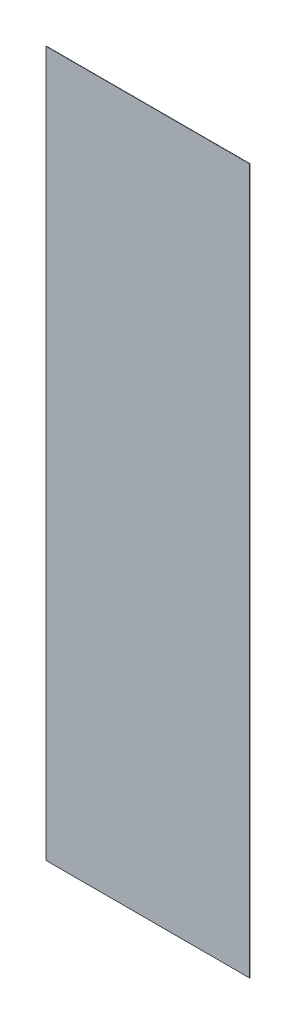
SolidWorks part; units mm, degrees
material "Ti-6Al-4VSolution treated and aged (SS)"
ref_plane "Front Plane" through (0, 0, 0) normal (0, 0, 1) x (1, 0, 0)
ref_plane "Top Plane" through (0, 0, 0) normal (0, 1, 0) x (1, 0, 0)
ref_plane "Right Plane" through (0, 0, 0) normal (1, 0, 0) x (0, 0, -1)
sketch "Sketch3" plane through (0, 0, 0) normal (0, 1, 0) x (1, 0, 0)
  line L0 (-693.76, 0) -> (693.76, 0)
  line L1 (693.76, 0) -> (694.3374, 1)
  line L2 (694.3374, 1) -> (-694.3374, 1)
  line L3 (0, 0) -> (0, 738.7484) construction
  line L5 (0, 1) -> (0, 0) construction
  line L6 (-693.76, 0) -> (-694.3374, 1)
  dimension "D1" = 693.76
  dimension "D2" = 120
  dimension "D3" = 1
extrude "Boss-Extrude1" add sketch "Sketch3" against normal blind 4810
chamfer "Chamfer1" distance 1 angle 45 1 edges at (0, 0, 0)
sketch "Sketch5" plane through (-521.1854, 0, -300.9065) normal (-0.866, 0, -0.5) x (-0.5, 0, 0.866)
  circle A0 centre (485.0344, -4772) radius 4.7625
  circle A1 centre (535.0344, -4772) radius 4.7625
  circle A2 centre (585.0344, -4772) radius 4.7625
  circle A3 centre (635.0344, -4772) radius 4.7625
  circle A4 centre (685.0344, -4772) radius 4.7625
  circle A5 centre (735.0344, -4772) radius 4.7625
  circle A6 centre (785.0344, -4772) radius 4.7625
  circle A7 centre (835.0344, -4772) radius 4.7625
  circle A8 centre (885.0344, -4772) radius 4.7625
  circle A9 centre (935.0344, -4772) radius 4.7625
  circle A10 centre (985.0344, -4772) radius 4.7625
  circle A11 centre (1035.0344, -4772) radius 4.7625
  circle A12 centre (1085.0344, -4772) radius 4.7625
  circle A13 centre (1135.0344, -4772) radius 4.7625
  circle A14 centre (1185.0344, -4772) radius 4.7625
  circle A15 centre (1235.0344, -4772) radius 4.7625
  circle A16 centre (1285.0344, -4772) radius 4.7625
  circle A17 centre (1335.0344, -4772) radius 4.7625
  circle A18 centre (1385.0344, -4772) radius 4.7625
  circle A19 centre (1435.0344, -4772) radius 4.7625
  circle A20 centre (1485.0344, -4772) radius 4.7625
  circle A21 centre (1535.0344, -4772) radius 4.7625
  circle A22 centre (1585.0344, -4772) radius 4.7625
  circle A23 centre (535.0344, -222) radius 4.7625
  circle A24 centre (585.0344, -222) radius 4.7625
  circle A25 centre (635.0344, -222) radius 4.7625
  circle A26 centre (685.0344, -222) radius 4.7625
  circle A27 centre (735.0344, -222) radius 4.7625
  circle A28 centre (785.0344, -222) radius 4.7625
  circle A29 centre (835.0344, -222) radius 4.7625
  circle A30 centre (885.0344, -222) radius 4.7625
  circle A31 centre (935.0344, -222) radius 4.7625
  circle A32 centre (985.0344, -222) radius 4.7625
  circle A33 centre (1035.0344, -222) radius 4.7625
  circle A34 centre (1085.0344, -222) radius 4.7625
  circle A35 centre (1135.0344, -222) radius 4.7625
  circle A36 centre (1185.0344, -222) radius 4.7625
  circle A37 centre (1235.0344, -222) radius 4.7625
  circle A38 centre (1285.0344, -222) radius 4.7625
  circle A39 centre (1335.0344, -222) radius 4.7625
  circle A40 centre (1385.0344, -222) radius 4.7625
  circle A41 centre (1435.0344, -222) radius 4.7625
  circle A42 centre (1485.0344, -222) radius 4.7625
  circle A43 centre (1535.0344, -222) radius 4.7625
  circle A44 centre (1585.0344, -222) radius 4.7625
  circle A45 centre (485.0344, -222) radius 4.7625
  circle A46 centre (1035.0344, -222) radius 4.7625
  circle A47 centre (1035.0344, -272) radius 4.7625
  circle A48 centre (1035.0344, -322) radius 4.7625
  circle A49 centre (1035.0344, -372) radius 4.7625
  circle A50 centre (1035.0344, -422) radius 4.7625
  circle A51 centre (1035.0344, -472) radius 4.7625
  circle A52 centre (1035.0344, -522) radius 4.7625
  circle A53 centre (1035.0344, -572) radius 4.7625
  circle A54 centre (1035.0344, -622) radius 4.7625
  circle A55 centre (1035.0344, -672) radius 4.7625
  circle A56 centre (1035.0344, -722) radius 4.7625
  circle A57 centre (1035.0344, -772) radius 4.7625
  circle A58 centre (1035.0344, -822) radius 4.7625
  circle A59 centre (1035.0344, -872) radius 4.7625
  circle A60 centre (1035.0344, -922) radius 4.7625
  circle A61 centre (1035.0344, -972) radius 4.7625
  circle A62 centre (1035.0344, -1022) radius 4.7625
  circle A63 centre (1035.0344, -1072) radius 4.7625
  circle A64 centre (1035.0344, -1122) radius 4.7625
  circle A65 centre (1035.0344, -1172) radius 4.7625
  circle A66 centre (1035.0344, -1222) radius 4.7625
  circle A67 centre (1035.0344, -1272) radius 4.7625
  circle A68 centre (1035.0344, -1322) radius 4.7625
  circle A69 centre (1035.0344, -1372) radius 4.7625
  circle A70 centre (1035.0344, -1422) radius 4.7625
  circle A71 centre (1035.0344, -1472) radius 4.7625
  circle A72 centre (1035.0344, -1522) radius 4.7625
  circle A73 centre (1035.0344, -1572) radius 4.7625
  circle A74 centre (1035.0344, -1622) radius 4.7625
  circle A75 centre (1035.0344, -1672) radius 4.7625
  circle A76 centre (1035.0344, -1722) radius 4.7625
  circle A77 centre (1035.0344, -1772) radius 4.7625
  circle A78 centre (1035.0344, -1822) radius 4.7625
  circle A79 centre (1035.0344, -1872) radius 4.7625
  circle A80 centre (1035.0344, -1922) radius 4.7625
  circle A81 centre (1035.0344, -1972) radius 4.7625
  circle A82 centre (1035.0344, -2022) radius 4.7625
  circle A83 centre (1035.0344, -2072) radius 4.7625
  circle A84 centre (1035.0344, -2122) radius 4.7625
  circle A85 centre (1035.0344, -2172) radius 4.7625
  circle A86 centre (1035.0344, -2222) radius 4.7625
  circle A87 centre (1035.0344, -2272) radius 4.7625
  circle A88 centre (1035.0344, -2322) radius 4.7625
  circle A89 centre (1035.0344, -2372) radius 4.7625
  circle A90 centre (1035.0344, -2422) radius 4.7625
  circle A91 centre (1035.0344, -2472) radius 4.7625
  circle A92 centre (1035.0344, -2522) radius 4.7625
  circle A93 centre (1035.0344, -2572) radius 4.7625
  circle A94 centre (1035.0344, -2622) radius 4.7625
  circle A95 centre (1035.0344, -2672) radius 4.7625
  circle A96 centre (1035.0344, -2722) radius 4.7625
  circle A97 centre (1035.0344, -2772) radius 4.7625
  circle A98 centre (1035.0344, -2822) radius 4.7625
  circle A99 centre (1035.0344, -2872) radius 4.7625
  circle A100 centre (1035.0344, -2922) radius 4.7625
  circle A101 centre (1035.0344, -2972) radius 4.7625
  circle A102 centre (1035.0344, -3022) radius 4.7625
  circle A103 centre (1035.0344, -3072) radius 4.7625
  circle A104 centre (1035.0344, -3122) radius 4.7625
  circle A105 centre (1035.0344, -3172) radius 4.7625
  circle A106 centre (1035.0344, -3222) radius 4.7625
  circle A107 centre (1035.0344, -3272) radius 4.7625
  circle A108 centre (1035.0344, -3322) radius 4.7625
  circle A109 centre (1035.0344, -3372) radius 4.7625
  circle A110 centre (1035.0344, -3422) radius 4.7625
  circle A111 centre (1035.0344, -3472) radius 4.7625
  circle A112 centre (1035.0344, -3522) radius 4.7625
  circle A113 centre (1035.0344, -3572) radius 4.7625
  circle A114 centre (1035.0344, -3622) radius 4.7625
  circle A115 centre (1035.0344, -3672) radius 4.7625
  circle A116 centre (1035.0344, -3722) radius 4.7625
  circle A117 centre (1035.0344, -3772) radius 4.7625
  circle A118 centre (1035.0344, -3822) radius 4.7625
  circle A119 centre (1035.0344, -3872) radius 4.7625
  circle A120 centre (1035.0344, -3922) radius 4.7625
  circle A121 centre (1035.0344, -3972) radius 4.7625
  circle A122 centre (1035.0344, -4022) radius 4.7625
  circle A123 centre (1035.0344, -4072) radius 4.7625
  circle A124 centre (1035.0344, -4122) radius 4.7625
  circle A125 centre (1035.0344, -4172) radius 4.7625
  circle A126 centre (1035.0344, -4222) radius 4.7625
  circle A127 centre (1035.0344, -4272) radius 4.7625
  circle A128 centre (1035.0344, -4322) radius 4.7625
  circle A129 centre (1035.0344, -4372) radius 4.7625
  circle A130 centre (1035.0344, -4422) radius 4.7625
  circle A131 centre (1035.0344, -4472) radius 4.7625
  circle A132 centre (1035.0344, -4522) radius 4.7625
  circle A133 centre (1035.0344, -4572) radius 4.7625
  circle A134 centre (1035.0344, -4622) radius 4.7625
  circle A135 centre (1035.0344, -4672) radius 4.7625
  circle A136 centre (1035.0344, -4722) radius 4.7625
  circle A137 centre (1035.0344, -4772) radius 4.7625
  circle A138 centre (485.0344, -272) radius 4.7625
  circle A139 centre (485.0344, -322) radius 4.7625
  circle A140 centre (485.0344, -372) radius 4.7625
  circle A141 centre (485.0344, -422) radius 4.7625
  circle A142 centre (485.0344, -472) radius 4.7625
  circle A143 centre (485.0344, -522) radius 4.7625
  circle A144 centre (485.0344, -572) radius 4.7625
  circle A145 centre (485.0344, -622) radius 4.7625
  circle A146 centre (485.0344, -672) radius 4.7625
  circle A147 centre (485.0344, -722) radius 4.7625
  circle A148 centre (485.0344, -772) radius 4.7625
  circle A149 centre (485.0344, -822) radius 4.7625
  circle A150 centre (485.0344, -872) radius 4.7625
  circle A151 centre (485.0344, -922) radius 4.7625
  circle A152 centre (485.0344, -972) radius 4.7625
  circle A153 centre (485.0344, -1022) radius 4.7625
  circle A154 centre (485.0344, -1072) radius 4.7625
  circle A155 centre (485.0344, -1122) radius 4.7625
  circle A156 centre (485.0344, -1172) radius 4.7625
  circle A157 centre (485.0344, -1222) radius 4.7625
  circle A158 centre (485.0344, -1272) radius 4.7625
  circle A159 centre (485.0344, -1322) radius 4.7625
  circle A160 centre (485.0344, -1372) radius 4.7625
  circle A161 centre (485.0344, -1422) radius 4.7625
  circle A162 centre (485.0344, -1472) radius 4.7625
  circle A163 centre (485.0344, -1522) radius 4.7625
  circle A164 centre (485.0344, -1572) radius 4.7625
  circle A165 centre (485.0344, -1622) radius 4.7625
  circle A166 centre (485.0344, -1672) radius 4.7625
  circle A167 centre (485.0344, -1722) radius 4.7625
  circle A168 centre (485.0344, -1772) radius 4.7625
  circle A169 centre (485.0344, -1822) radius 4.7625
  circle A170 centre (485.0344, -1872) radius 4.7625
  circle A171 centre (485.0344, -1922) radius 4.7625
  circle A172 centre (485.0344, -1972) radius 4.7625
  circle A173 centre (485.0344, -2022) radius 4.7625
  circle A174 centre (485.0344, -2072) radius 4.7625
  circle A175 centre (485.0344, -2122) radius 4.7625
  circle A176 centre (485.0344, -2172) radius 4.7625
  circle A177 centre (485.0344, -2222) radius 4.7625
  circle A178 centre (485.0344, -2272) radius 4.7625
  circle A179 centre (485.0344, -2322) radius 4.7625
  circle A180 centre (485.0344, -2372) radius 4.7625
  circle A181 centre (485.0344, -2422) radius 4.7625
  circle A182 centre (485.0344, -2472) radius 4.7625
  circle A183 centre (485.0344, -2522) radius 4.7625
  circle A184 centre (485.0344, -2572) radius 4.7625
  circle A185 centre (485.0344, -2622) radius 4.7625
  circle A186 centre (485.0344, -2672) radius 4.7625
  circle A187 centre (485.0344, -2722) radius 4.7625
  circle A188 centre (485.0344, -2772) radius 4.7625
  circle A189 centre (485.0344, -2822) radius 4.7625
  circle A190 centre (485.0344, -2872) radius 4.7625
  circle A191 centre (485.0344, -2922) radius 4.7625
  circle A192 centre (485.0344, -2972) radius 4.7625
  circle A193 centre (485.0344, -3022) radius 4.7625
  circle A194 centre (485.0344, -3072) radius 4.7625
  circle A195 centre (485.0344, -3122) radius 4.7625
  circle A196 centre (485.0344, -3172) radius 4.7625
  circle A197 centre (485.0344, -3222) radius 4.7625
  circle A198 centre (485.0344, -3272) radius 4.7625
  circle A199 centre (485.0344, -3322) radius 4.7625
  circle A200 centre (485.0344, -3372) radius 4.7625
  circle A201 centre (485.0344, -3422) radius 4.7625
  circle A202 centre (485.0344, -3472) radius 4.7625
  circle A203 centre (485.0344, -3522) radius 4.7625
  circle A204 centre (485.0344, -3572) radius 4.7625
  circle A205 centre (485.0344, -3622) radius 4.7625
  circle A206 centre (485.0344, -3672) radius 4.7625
  circle A207 centre (485.0344, -3722) radius 4.7625
  circle A208 centre (485.0344, -3772) radius 4.7625
  circle A209 centre (485.0344, -3822) radius 4.7625
  circle A210 centre (485.0344, -3872) radius 4.7625
  circle A211 centre (485.0344, -3922) radius 4.7625
  circle A212 centre (485.0344, -3972) radius 4.7625
  circle A213 centre (485.0344, -4022) radius 4.7625
  circle A214 centre (485.0344, -4072) radius 4.7625
  circle A215 centre (485.0344, -4122) radius 4.7625
  circle A216 centre (485.0344, -4172) radius 4.7625
  circle A217 centre (485.0344, -4222) radius 4.7625
  circle A218 centre (485.0344, -4272) radius 4.7625
  circle A219 centre (485.0344, -4322) radius 4.7625
  circle A220 centre (485.0344, -4372) radius 4.7625
  circle A221 centre (485.0344, -4422) radius 4.7625
  circle A222 centre (485.0344, -4472) radius 4.7625
  circle A223 centre (485.0344, -4522) radius 4.7625
  circle A224 centre (485.0344, -4572) radius 4.7625
  circle A225 centre (485.0344, -4622) radius 4.7625
  circle A226 centre (485.0344, -4672) radius 4.7625
  circle A227 centre (485.0344, -4722) radius 4.7625
  circle A228 centre (485.0344, -4772) radius 4.7625
  circle A229 centre (1035.0344, -4772) radius 4.7625
  circle A230 centre (1585.0344, -4772) radius 4.7625
  circle A231 centre (1035.0344, -4722) radius 4.7625
  circle A232 centre (1585.0344, -4722) radius 4.7625
  circle A233 centre (1035.0344, -4672) radius 4.7625
  circle A234 centre (1585.0344, -4672) radius 4.7625
  circle A235 centre (1035.0344, -4622) radius 4.7625
  circle A236 centre (1585.0344, -4622) radius 4.7625
  circle A237 centre (1035.0344, -4572) radius 4.7625
  circle A238 centre (1585.0344, -4572) radius 4.7625
  circle A239 centre (1035.0344, -4522) radius 4.7625
  circle A240 centre (1585.0344, -4522) radius 4.7625
  circle A241 centre (1035.0344, -4472) radius 4.7625
  circle A242 centre (1585.0344, -4472) radius 4.7625
  circle A243 centre (1035.0344, -4422) radius 4.7625
  circle A244 centre (1585.0344, -4422) radius 4.7625
  circle A245 centre (1035.0344, -4372) radius 4.7625
  circle A246 centre (1585.0344, -4372) radius 4.7625
  circle A247 centre (1035.0344, -4322) radius 4.7625
  circle A248 centre (1585.0344, -4322) radius 4.7625
  circle A249 centre (1035.0344, -4272) radius 4.7625
  circle A250 centre (1585.0344, -4272) radius 4.7625
  circle A251 centre (1035.0344, -4222) radius 4.7625
  circle A252 centre (1585.0344, -4222) radius 4.7625
  circle A253 centre (1035.0344, -4172) radius 4.7625
  circle A254 centre (1585.0344, -4172) radius 4.7625
  circle A255 centre (1035.0344, -4122) radius 4.7625
  circle A256 centre (1585.0344, -4122) radius 4.7625
  circle A257 centre (1035.0344, -4072) radius 4.7625
  circle A258 centre (1585.0344, -4072) radius 4.7625
  circle A259 centre (1035.0344, -4022) radius 4.7625
  circle A260 centre (1585.0344, -4022) radius 4.7625
  circle A261 centre (1035.0344, -3972) radius 4.7625
  circle A262 centre (1585.0344, -3972) radius 4.7625
  circle A263 centre (1035.0344, -3922) radius 4.7625
  circle A264 centre (1585.0344, -3922) radius 4.7625
  circle A265 centre (1035.0344, -3872) radius 4.7625
  circle A266 centre (1585.0344, -3872) radius 4.7625
  circle A267 centre (1035.0344, -3822) radius 4.7625
  circle A268 centre (1585.0344, -3822) radius 4.7625
  circle A269 centre (1035.0344, -3772) radius 4.7625
  circle A270 centre (1585.0344, -3772) radius 4.7625
  circle A271 centre (1035.0344, -3722) radius 4.7625
  circle A272 centre (1585.0344, -3722) radius 4.7625
  circle A273 centre (1035.0344, -3672) radius 4.7625
  circle A274 centre (1585.0344, -3672) radius 4.7625
  circle A275 centre (1035.0344, -3622) radius 4.7625
  circle A276 centre (1585.0344, -3622) radius 4.7625
  circle A277 centre (1035.0344, -3572) radius 4.7625
  circle A278 centre (1585.0344, -3572) radius 4.7625
  circle A279 centre (1035.0344, -3522) radius 4.7625
  circle A280 centre (1585.0344, -3522) radius 4.7625
  circle A281 centre (1035.0344, -3472) radius 4.7625
  circle A282 centre (1585.0344, -3472) radius 4.7625
  circle A283 centre (1035.0344, -3422) radius 4.7625
  circle A284 centre (1585.0344, -3422) radius 4.7625
  circle A285 centre (1035.0344, -3372) radius 4.7625
  circle A286 centre (1585.0344, -3372) radius 4.7625
  circle A287 centre (1035.0344, -3322) radius 4.7625
  circle A288 centre (1585.0344, -3322) radius 4.7625
  circle A289 centre (1035.0344, -3272) radius 4.7625
  circle A290 centre (1585.0344, -3272) radius 4.7625
  circle A291 centre (1035.0344, -3222) radius 4.7625
  circle A292 centre (1585.0344, -3222) radius 4.7625
  circle A293 centre (1035.0344, -3172) radius 4.7625
  circle A294 centre (1585.0344, -3172) radius 4.7625
  circle A295 centre (1035.0344, -3122) radius 4.7625
  circle A296 centre (1585.0344, -3122) radius 4.7625
  circle A297 centre (1035.0344, -3072) radius 4.7625
  circle A298 centre (1585.0344, -3072) radius 4.7625
  circle A299 centre (1035.0344, -3022) radius 4.7625
  circle A300 centre (1585.0344, -3022) radius 4.7625
  circle A301 centre (1035.0344, -2972) radius 4.7625
  circle A302 centre (1585.0344, -2972) radius 4.7625
  circle A303 centre (1035.0344, -2922) radius 4.7625
  circle A304 centre (1585.0344, -2922) radius 4.7625
  circle A305 centre (1035.0344, -2872) radius 4.7625
  circle A306 centre (1585.0344, -2872) radius 4.7625
  circle A307 centre (1035.0344, -2822) radius 4.7625
  circle A308 centre (1585.0344, -2822) radius 4.7625
  circle A309 centre (1035.0344, -2772) radius 4.7625
  circle A310 centre (1585.0344, -2772) radius 4.7625
  circle A311 centre (1035.0344, -2722) radius 4.7625
  circle A312 centre (1585.0344, -2722) radius 4.7625
  circle A313 centre (1035.0344, -2672) radius 4.7625
  circle A314 centre (1585.0344, -2672) radius 4.7625
  circle A315 centre (1035.0344, -2622) radius 4.7625
  circle A316 centre (1585.0344, -2622) radius 4.7625
  circle A317 centre (1035.0344, -2572) radius 4.7625
  circle A318 centre (1585.0344, -2572) radius 4.7625
  circle A319 centre (1035.0344, -2522) radius 4.7625
  circle A320 centre (1585.0344, -2522) radius 4.7625
  circle A321 centre (1035.0344, -2472) radius 4.7625
  circle A322 centre (1585.0344, -2472) radius 4.7625
  circle A323 centre (1035.0344, -2422) radius 4.7625
  circle A324 centre (1585.0344, -2422) radius 4.7625
  circle A325 centre (1035.0344, -2372) radius 4.7625
  circle A326 centre (1585.0344, -2372) radius 4.7625
  circle A327 centre (1035.0344, -2322) radius 4.7625
  circle A328 centre (1585.0344, -2322) radius 4.7625
  circle A329 centre (1035.0344, -2272) radius 4.7625
  circle A330 centre (1585.0344, -2272) radius 4.7625
  circle A331 centre (1035.0344, -2222) radius 4.7625
  circle A332 centre (1585.0344, -2222) radius 4.7625
  circle A333 centre (1035.0344, -2172) radius 4.7625
  circle A334 centre (1585.0344, -2172) radius 4.7625
  circle A335 centre (1035.0344, -2122) radius 4.7625
  circle A336 centre (1585.0344, -2122) radius 4.7625
  circle A337 centre (1035.0344, -2072) radius 4.7625
  circle A338 centre (1585.0344, -2072) radius 4.7625
  circle A339 centre (1035.0344, -2022) radius 4.7625
  circle A340 centre (1585.0344, -2022) radius 4.7625
  circle A341 centre (1035.0344, -1972) radius 4.7625
  circle A342 centre (1585.0344, -1972) radius 4.7625
  circle A343 centre (1035.0344, -1922) radius 4.7625
  circle A344 centre (1585.0344, -1922) radius 4.7625
  circle A345 centre (1035.0344, -1872) radius 4.7625
  circle A346 centre (1585.0344, -1872) radius 4.7625
  circle A347 centre (1035.0344, -1822) radius 4.7625
  circle A348 centre (1585.0344, -1822) radius 4.7625
  circle A349 centre (1035.0344, -1772) radius 4.7625
  circle A350 centre (1585.0344, -1772) radius 4.7625
  circle A351 centre (1035.0344, -1722) radius 4.7625
  circle A352 centre (1585.0344, -1722) radius 4.7625
  circle A353 centre (1035.0344, -1672) radius 4.7625
  circle A354 centre (1585.0344, -1672) radius 4.7625
  circle A355 centre (1035.0344, -1622) radius 4.7625
  circle A356 centre (1585.0344, -1622) radius 4.7625
  circle A357 centre (1035.0344, -1572) radius 4.7625
  circle A358 centre (1585.0344, -1572) radius 4.7625
  circle A359 centre (1035.0344, -1522) radius 4.7625
  circle A360 centre (1585.0344, -1522) radius 4.7625
  circle A361 centre (1035.0344, -1472) radius 4.7625
  circle A362 centre (1585.0344, -1472) radius 4.7625
  circle A363 centre (1035.0344, -1422) radius 4.7625
  circle A364 centre (1585.0344, -1422) radius 4.7625
  circle A365 centre (1035.0344, -1372) radius 4.7625
  circle A366 centre (1585.0344, -1372) radius 4.7625
  circle A367 centre (1035.0344, -1322) radius 4.7625
  circle A368 centre (1585.0344, -1322) radius 4.7625
  circle A369 centre (1035.0344, -1272) radius 4.7625
  circle A370 centre (1585.0344, -1272) radius 4.7625
  circle A371 centre (1035.0344, -1222) radius 4.7625
  circle A372 centre (1585.0344, -1222) radius 4.7625
  circle A373 centre (1035.0344, -1172) radius 4.7625
  circle A374 centre (1585.0344, -1172) radius 4.7625
  circle A375 centre (1035.0344, -1122) radius 4.7625
  circle A376 centre (1585.0344, -1122) radius 4.7625
  circle A377 centre (1035.0344, -1072) radius 4.7625
  circle A378 centre (1585.0344, -1072) radius 4.7625
  circle A379 centre (1035.0344, -1022) radius 4.7625
  circle A380 centre (1585.0344, -1022) radius 4.7625
  circle A381 centre (1035.0344, -972) radius 4.7625
  circle A382 centre (1585.0344, -972) radius 4.7625
  circle A383 centre (1035.0344, -922) radius 4.7625
  circle A384 centre (1585.0344, -922) radius 4.7625
  circle A385 centre (1035.0344, -872) radius 4.7625
  circle A386 centre (1585.0344, -872) radius 4.7625
  circle A387 centre (1035.0344, -822) radius 4.7625
  circle A388 centre (1585.0344, -822) radius 4.7625
  circle A389 centre (1035.0344, -772) radius 4.7625
  circle A390 centre (1585.0344, -772) radius 4.7625
  circle A391 centre (1035.0344, -722) radius 4.7625
  circle A392 centre (1585.0344, -722) radius 4.7625
  circle A393 centre (1035.0344, -672) radius 4.7625
  circle A394 centre (1585.0344, -672) radius 4.7625
  circle A395 centre (1035.0344, -622) radius 4.7625
  circle A396 centre (1585.0344, -622) radius 4.7625
  circle A397 centre (1035.0344, -572) radius 4.7625
  circle A398 centre (1585.0344, -572) radius 4.7625
  circle A399 centre (1035.0344, -522) radius 4.7625
  circle A400 centre (1585.0344, -522) radius 4.7625
  circle A401 centre (1035.0344, -472) radius 4.7625
  circle A402 centre (1585.0344, -472) radius 4.7625
  circle A403 centre (1035.0344, -422) radius 4.7625
  circle A404 centre (1585.0344, -422) radius 4.7625
  circle A405 centre (1035.0344, -372) radius 4.7625
  circle A406 centre (1585.0344, -372) radius 4.7625
  circle A407 centre (1035.0344, -322) radius 4.7625
  circle A408 centre (1585.0344, -322) radius 4.7625
  circle A409 centre (1035.0344, -272) radius 4.7625
  circle A410 centre (1585.0344, -272) radius 4.7625
  circle A411 centre (1035.0344, -222) radius 4.7625
  circle A412 centre (1585.0344, -222) radius 4.7625
  circle A413 centre (485.0344, -4722) radius 4.7625
  circle A414 centre (485.0344, -4672) radius 4.7625
  circle A415 centre (485.0344, -4622) radius 4.7625
  circle A416 centre (485.0344, -4572) radius 4.7625
  circle A417 centre (485.0344, -4522) radius 4.7625
  circle A418 centre (485.0344, -4472) radius 4.7625
  circle A419 centre (485.0344, -4422) radius 4.7625
  circle A420 centre (485.0344, -4372) radius 4.7625
  circle A421 centre (485.0344, -4322) radius 4.7625
  circle A422 centre (485.0344, -4272) radius 4.7625
  circle A423 centre (485.0344, -4222) radius 4.7625
  circle A424 centre (485.0344, -4172) radius 4.7625
  circle A425 centre (485.0344, -4122) radius 4.7625
  circle A426 centre (485.0344, -4072) radius 4.7625
  circle A427 centre (485.0344, -4022) radius 4.7625
  circle A428 centre (485.0344, -3972) radius 4.7625
  circle A429 centre (485.0344, -3922) radius 4.7625
  circle A430 centre (485.0344, -3872) radius 4.7625
  circle A431 centre (485.0344, -3822) radius 4.7625
  circle A432 centre (485.0344, -3772) radius 4.7625
  circle A433 centre (485.0344, -3722) radius 4.7625
  circle A434 centre (485.0344, -3672) radius 4.7625
  circle A435 centre (485.0344, -3622) radius 4.7625
  circle A436 centre (485.0344, -3572) radius 4.7625
  circle A437 centre (485.0344, -3522) radius 4.7625
  circle A438 centre (485.0344, -3472) radius 4.7625
  circle A439 centre (485.0344, -3422) radius 4.7625
  circle A440 centre (485.0344, -3372) radius 4.7625
  circle A441 centre (485.0344, -3322) radius 4.7625
  circle A442 centre (485.0344, -3272) radius 4.7625
  circle A443 centre (485.0344, -3222) radius 4.7625
  circle A444 centre (485.0344, -3172) radius 4.7625
  circle A445 centre (485.0344, -3122) radius 4.7625
  circle A446 centre (485.0344, -3072) radius 4.7625
  circle A447 centre (485.0344, -3022) radius 4.7625
  circle A448 centre (485.0344, -2972) radius 4.7625
  circle A449 centre (485.0344, -2922) radius 4.7625
  circle A450 centre (485.0344, -2872) radius 4.7625
  circle A451 centre (485.0344, -2822) radius 4.7625
  circle A452 centre (485.0344, -2772) radius 4.7625
  circle A453 centre (485.0344, -2722) radius 4.7625
  circle A454 centre (485.0344, -2672) radius 4.7625
  circle A455 centre (485.0344, -2622) radius 4.7625
  circle A456 centre (485.0344, -2572) radius 4.7625
  circle A457 centre (485.0344, -2522) radius 4.7625
  circle A458 centre (485.0344, -2472) radius 4.7625
  circle A459 centre (485.0344, -2422) radius 4.7625
  circle A460 centre (485.0344, -2372) radius 4.7625
  circle A461 centre (485.0344, -2322) radius 4.7625
  circle A462 centre (485.0344, -2272) radius 4.7625
  circle A463 centre (485.0344, -2222) radius 4.7625
  circle A464 centre (485.0344, -2172) radius 4.7625
  circle A465 centre (485.0344, -2122) radius 4.7625
  circle A466 centre (485.0344, -2072) radius 4.7625
  circle A467 centre (485.0344, -2022) radius 4.7625
  circle A468 centre (485.0344, -1972) radius 4.7625
  circle A469 centre (485.0344, -1922) radius 4.7625
  circle A470 centre (485.0344, -1872) radius 4.7625
  circle A471 centre (485.0344, -1822) radius 4.7625
  circle A472 centre (485.0344, -1772) radius 4.7625
  circle A473 centre (485.0344, -1722) radius 4.7625
  circle A474 centre (485.0344, -1672) radius 4.7625
  circle A475 centre (485.0344, -1622) radius 4.7625
  circle A476 centre (485.0344, -1572) radius 4.7625
  circle A477 centre (485.0344, -1522) radius 4.7625
  circle A478 centre (485.0344, -1472) radius 4.7625
  circle A479 centre (485.0344, -1422) radius 4.7625
  circle A480 centre (485.0344, -1372) radius 4.7625
  circle A481 centre (485.0344, -1322) radius 4.7625
  circle A482 centre (485.0344, -1272) radius 4.7625
  circle A483 centre (485.0344, -1222) radius 4.7625
  circle A484 centre (485.0344, -1172) radius 4.7625
  circle A485 centre (485.0344, -1122) radius 4.7625
  circle A486 centre (485.0344, -1072) radius 4.7625
  circle A487 centre (485.0344, -1022) radius 4.7625
  circle A488 centre (485.0344, -972) radius 4.7625
  circle A489 centre (485.0344, -922) radius 4.7625
  circle A490 centre (485.0344, -872) radius 4.7625
  circle A491 centre (485.0344, -822) radius 4.7625
  circle A492 centre (485.0344, -772) radius 4.7625
  circle A493 centre (485.0344, -722) radius 4.7625
  circle A494 centre (485.0344, -672) radius 4.7625
  circle A495 centre (485.0344, -622) radius 4.7625
  circle A496 centre (485.0344, -572) radius 4.7625
  circle A497 centre (485.0344, -522) radius 4.7625
  circle A498 centre (485.0344, -472) radius 4.7625
  circle A499 centre (485.0344, -422) radius 4.7625
  circle A500 centre (485.0344, -372) radius 4.7625
  circle A501 centre (485.0344, -322) radius 4.7625
  circle A502 centre (485.0344, -272) radius 4.7625
  circle A503 centre (485.0344, -222) radius 4.7625
  dimension "D1" = 23
  dimension "D2" = 2
  dimension "D3" = 2
  dimension "D4" = 92
  dimension "D5" = 3
  dimension "D6" = 92
